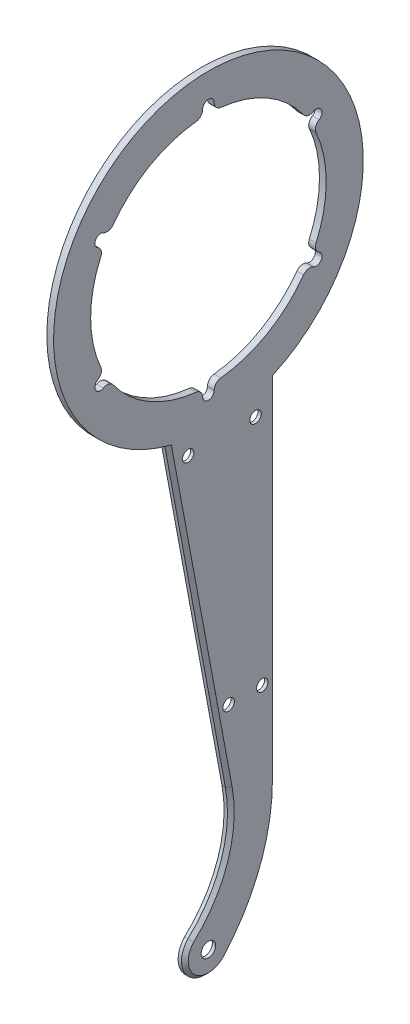
SolidWorks part; units mm, degrees
ref_plane "前视基准面" through (0, 0, 0) normal (0, 0, 1) x (1, 0, 0)
ref_plane "上视基准面" through (0, 0, 0) normal (0, 1, 0) x (1, 0, 0)
ref_plane "右视基准面" through (0, 0, 0) normal (1, 0, 0) x (0, 0, -1)
sketch "草图1" plane through (0, 0, 0) normal (1, 0, 0) x (0, 0, -1)
  line L10 (-12.0867, -44.3837) -> (6.0415, -141.8339)
  line L13 (20, -146.0922) -> (20, -41.4246)
  arc A21 (20, -41.4246) -> (-12.0867, -44.3837) centre (0, 0) ccw
  arc A22 (20, -146.0922) -> (5.2059, -184.6796) centre (-37.7208, -146.0922) cw
  arc A23 (5.2059, -184.6796) -> (-5.0762, -175.1801) centre (0, -180) cw
  circle A24 centre (0, -180) radius 2.15
  arc A25 (6.0415, -141.8339) -> (-5.0762, -175.1801) centre (-29.6255, -148.4689) cw
  circle A26 centre (-6, -50) radius 1.7
  circle A27 centre (14, -50) radius 1.7
  circle A28 centre (6, -120) radius 1.7
  circle A29 centre (16, -120) radius 1.7
  arc A30 (1.7, -37) -> (3.6883, -34.7898) centre (3.9226, -37) cw
  arc A33 (1.7, -37) -> (-1.7, -37) centre (0, -37) cw
  arc A34 (-1.7, -37) -> (-3.6883, -34.7898) centre (-3.9226, -37) ccw
  arc A35 (-32.8929, -17.0278) -> (-31.973, -14.2008) centre (-34.0042, -15.1029) ccw
  arc A36 (-31.1929, -19.9722) -> (-32.8929, -17.0278) centre (-32.0429, -18.5) cw
  arc A37 (-31.1929, -19.9722) -> (-28.2847, -20.589) centre (-30.0817, -21.8971) cw
  arc A38 (-31.1929, 19.9722) -> (-28.2847, 20.589) centre (-30.0817, 21.8971) ccw
  arc A39 (-32.8929, 17.0278) -> (-31.1929, 19.9722) centre (-32.0429, 18.5) cw
  arc A40 (-32.8929, 17.0278) -> (-31.973, 14.2008) centre (-34.0042, 15.1029) cw
  arc A41 (1.7, 37) -> (3.6883, 34.7898) centre (3.9226, 37) ccw
  arc A42 (-1.7, 37) -> (1.7, 37) centre (0, 37) cw
  arc A43 (-1.7, 37) -> (-3.6883, 34.7898) centre (-3.9226, 37) cw
  arc A44 (32.8929, 17.0278) -> (31.973, 14.2008) centre (34.0042, 15.1029) ccw
  arc A45 (31.1929, 19.9722) -> (32.8929, 17.0278) centre (32.0429, 18.5) cw
  arc A46 (31.1929, 19.9722) -> (28.2847, 20.589) centre (30.0817, 21.8971) cw
  arc A47 (31.1929, -19.9722) -> (28.2847, -20.589) centre (30.0817, -21.8971) ccw
  arc A48 (32.8929, -17.0278) -> (31.1929, -19.9722) centre (32.0429, -18.5) cw
  arc A49 (32.8929, -17.0278) -> (31.973, -14.2008) centre (34.0042, -15.1029) cw
  arc A50 (-31.973, 14.2008) -> (-31.973, -14.2008) centre (0, 0) ccw
  arc A51 (-28.2847, -20.589) -> (-3.6883, -34.7898) centre (0, 0) ccw
  arc A52 (28.2847, -20.589) -> (3.6883, -34.7898) centre (0, 0) cw
  arc A53 (31.973, 14.2008) -> (31.973, -14.2008) centre (0, 0) cw
  arc A54 (28.2847, 20.589) -> (3.6883, 34.7898) centre (0, 0) ccw
  arc A55 (-3.6883, 34.7898) -> (-28.2847, 20.589) centre (0, 0) ccw
  point P79 (0, 0)
extrude "凸台-拉伸3" add sketch "草图1" along normal blind 2
sketch "草图2" plane through (0, 0, 0) normal (-1, 0, 0) x (0, 0, 1)
  circle A0 centre (0, -180) radius 5
  circle A1 centre (-14, -50) radius 3.5
  circle A2 centre (6, -50) radius 3.5
  circle A3 centre (-16, -120) radius 3.5
  circle A4 centre (-6, -120) radius 3.5
  point P8 (6, -50)
  point P12 (-16, -120)
  point P16 (-6, -120)
extrude "切除-拉伸1" cut sketch "草图2" against normal blind 1
chamfer "倒角1" distance 1 angle 45 5 edges at (2, -93.1088, 3.0226) (2, -159.9434, -4.7909) (2, -185.1415, 4.7502) (2, -166.7553, -16.1747) (2, -93.7584, -20)
